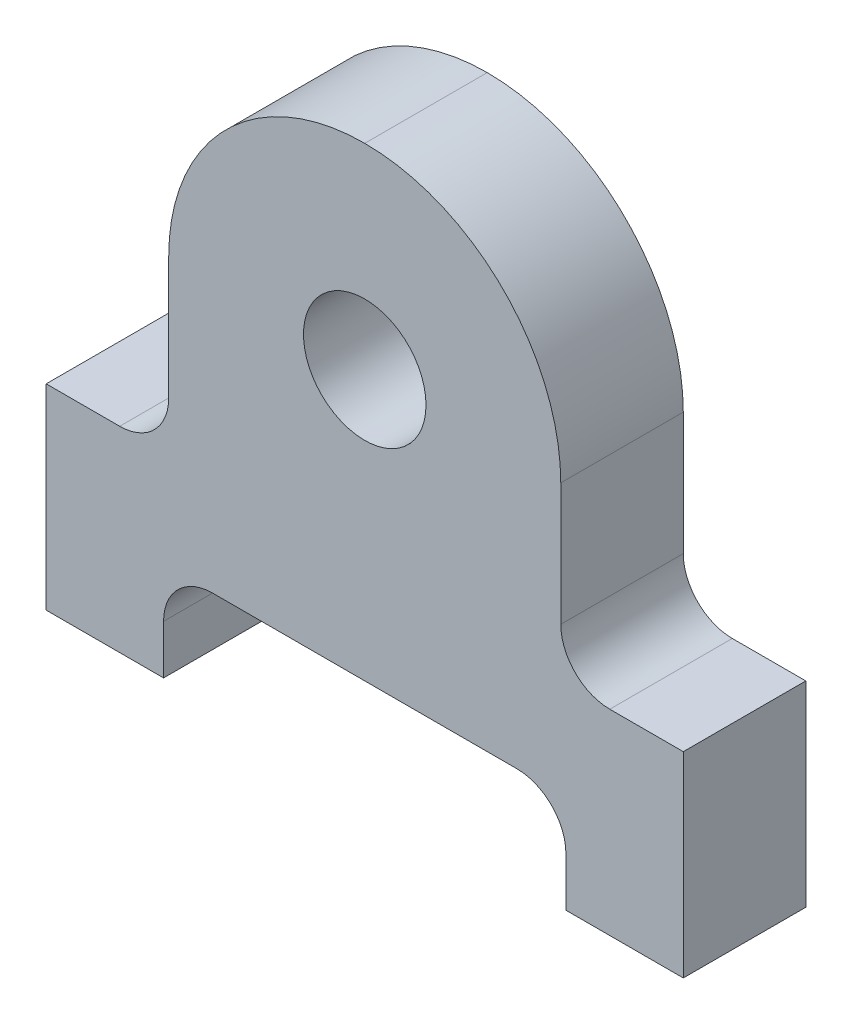
SolidWorks part; units mm, degrees
ref_plane "Front Plane" through (0, 0, 0) normal (0, 0, 1) x (1, 0, 0)
ref_plane "Top Plane" through (0, 0, 0) normal (0, 1, 0) x (1, 0, 0)
ref_plane "Right Plane" through (0, 0, 0) normal (1, 0, 0) x (0, 0, -1)
sketch "Sketch1" plane through (0, 0, 0) normal (0, 0, 1) x (1, 0, 0)
  line L1 (16.51, -14.605) -> (-16.51, -14.605)
  line L2 (16.51, -14.605) -> (16.51, 14.605)
  line L3 (16.51, 14.605) -> (-16.51, 14.605)
  line L4 (-16.51, -14.605) -> (-16.51, 14.605)
  line L5 (16.51, -14.605) -> (-16.51, 14.605) construction
  line L6 (16.51, 14.605) -> (-16.51, -14.605) construction
  point P0 (0, 0)
  dimension "D1" = 33.02
  dimension "D2" = 29.21
extrude "Boss-Extrude1" add sketch "Sketch1" along normal blind 6.35
sketch "Sketch2" plane through (0, 0, 6.35) normal (0, 0, 1) x (1, 0, 0)
  line L0 (-16.51, -4.445) -> (16.51, -4.445) construction
  line L1 (-16.51, 14.605) -> (-16.51, -14.605) construction
  line L2 (16.51, -14.605) -> (16.51, 14.605) construction
  line L3 (-16.51, -14.605) -> (16.51, -14.605) construction
  line L4 (-16.51, -9.525) -> (16.51, -9.525) construction
  line L5 (-16.51, -4.445) -> (-16.51, -14.605)
  line L6 (-10.4267, -14.605) -> (10.4267, -14.605) construction
  line L7 (-10.4267, -14.605) -> (-10.4267, -9.525)
  line L8 (-10.4267, -9.525) -> (10.4267, -9.525)
  line L9 (10.4267, -14.605) -> (10.4267, -9.525)
  line L10 (-16.51, -14.605) -> (-10.4267, -14.605)
  line L11 (16.51, -4.445) -> (16.51, -14.605)
  line L12 (16.51, -14.605) -> (10.4267, -14.605)
  line L13 (16.51, 14.605) -> (-16.51, 14.605) construction
  line L14 (-10.16, 14.605) -> (10.16, 14.605)
  line L15 (-10.16, 14.605) -> (-10.16, -4.445)
  line L16 (-10.16, -4.445) -> (10.16, -4.445) construction
  line L17 (10.16, 14.605) -> (10.16, -4.445)
  line L18 (-16.51, -4.445) -> (-10.16, -4.445)
  line L19 (10.16, -4.445) -> (16.51, -4.445)
  circle A0 centre (0, 4.445) radius 3.175
  point P17 (0, -9.525)
  point P28 (0, 14.605)
  dimension "D2" = 6.35
  dimension "D1" = 10.16
  dimension "D3" = 19.05
  dimension "D4" = 5.08
  dimension "D5" = 20.8534
  dimension "D6" = 20.32
sketch "Sketch3" plane through (0, 0, 6.35) normal (0, 0, 1) x (1, 0, 0)
  line L1 (-16.51, 14.605) -> (-10.16, 14.605)
  line L2 (-16.51, 14.605) -> (-16.51, -4.445)
  line L3 (-16.51, -4.445) -> (-10.16, -4.445)
  line L4 (-10.16, 14.605) -> (-10.16, -4.445)
  line L5 (10.16, 14.605) -> (16.51, 14.605)
  line L6 (10.16, 14.605) -> (10.16, -4.445)
  line L7 (10.16, -4.445) -> (16.51, -4.445)
  line L8 (16.51, 14.605) -> (16.51, -4.445)
  line L9 (-10.4267, -9.525) -> (10.4267, -9.525)
  line L10 (-10.4267, -9.525) -> (-10.4267, -14.605)
  line L11 (-10.4267, -14.605) -> (10.4267, -14.605)
  line L12 (10.4267, -9.525) -> (10.4267, -14.605)
  circle A0 centre (0, 4.445) radius 3.175
extrude "Cut-Extrude1" cut sketch "Sketch3" against normal up to next
fillet "Fillet1" radius 10.16 2 edges at (10.16, 14.605, 3.175) (-10.16, 14.605, 3.175)
fillet "Fillet2" radius 2.54 4 edges at (10.16, -4.445, 3.175) (-10.16, -4.445, 3.175) (10.4267, -9.525, 3.175) (-10.4267, -9.525, 3.175)
